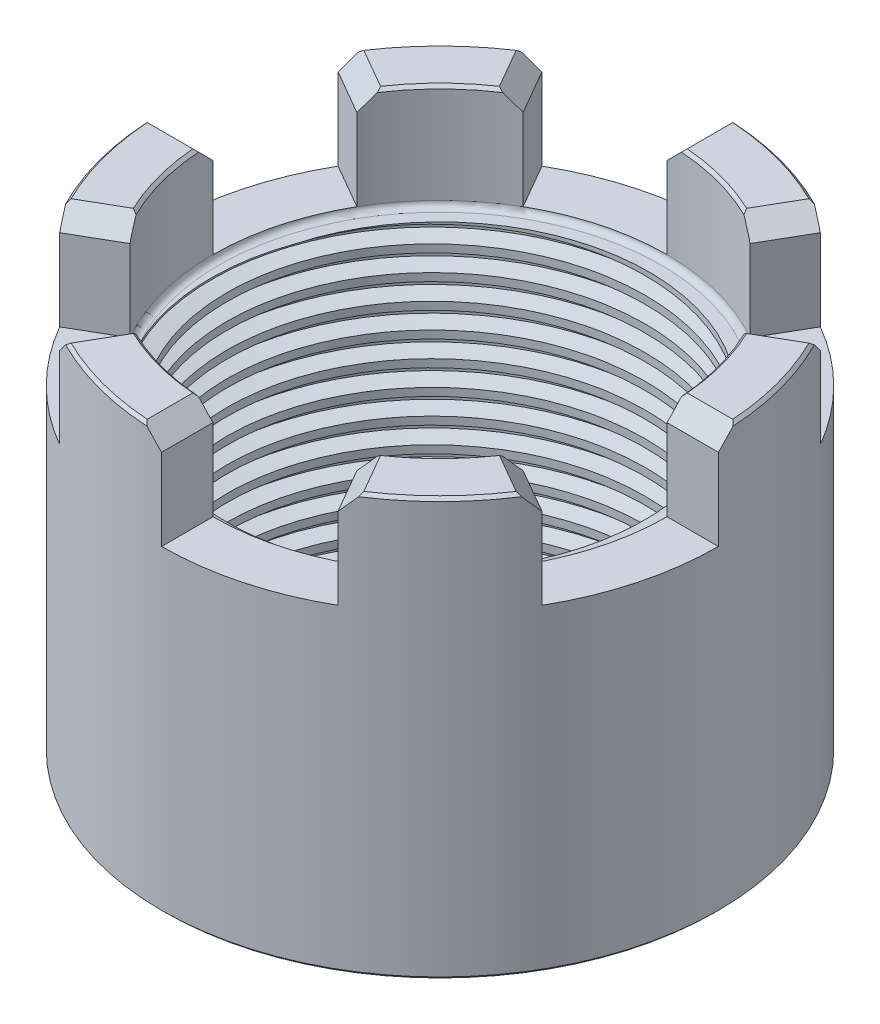
SolidWorks part; units mm, degrees
ref_plane "Front Plane" through (0, 0, 0) normal (0, 0, 1) x (1, 0, 0)
ref_plane "Top Plane" through (0, 0, 0) normal (0, 1, 0) x (1, 0, 0)
ref_plane "Right Plane" through (0, 0, 0) normal (1, 0, 0) x (0, 0, -1)
sketch "Sketch1" plane through (0, 0, 0) normal (0, 1, 0) x (1, 0, 0)
  circle A0 centre (0, 0) radius 35.56
  dimension "D1" = 71.12
extrude "Boss-Extrude1" add sketch "Sketch1" along normal blind 40.64
sketch "Sketch2" plane through (0, 40.64, 0) normal (0, 1, 0) x (1, 0, 0)
  circle A0 centre (0, 0) radius 26.7018
  dimension "D1" = 53.4035
extrude "Cut-Extrude1" cut sketch "Sketch2" against normal blind 67.31
sketch "Sketch3" plane through (0, 40.64, 0) normal (0, 1, 0) x (1, 0, 0)
  line L0 (-28.9941, 0) -> (-35.56, 0)
  line L1 (-25.1096, -14.4971) -> (-30.7959, -17.78)
  line L2 (-25.1096, 14.4971) -> (-30.7959, 17.78)
  line L3 (-14.497, 25.1096) -> (-17.78, 30.7959)
  line L4 (0, 28.9941) -> (0, 35.56)
  line L5 (14.4971, 25.1096) -> (17.78, 30.7959)
  line L6 (25.1096, 14.497) -> (30.7959, 17.78)
  line L7 (28.9941, 0) -> (35.56, 0)
  line L8 (25.1096, -14.4971) -> (30.7959, -17.78)
  line L9 (14.497, -25.1096) -> (17.78, -30.7959)
  line L10 (0, -28.9941) -> (0, -35.56)
  line L11 (-14.4971, -25.1096) -> (-17.78, -30.7959)
  arc A0 (-35.56, 0) -> (-30.7959, -17.78) centre (0, 0) ccw
  arc A1 (-28.9941, 0) -> (-25.1096, -14.4971) centre (0, 0) ccw
  arc A2 (-17.78, 30.7959) -> (-30.7959, 17.78) centre (0, 0) ccw
  arc A3 (-14.497, 25.1096) -> (-25.1096, 14.4971) centre (0, 0) ccw
  arc A4 (17.78, 30.7959) -> (0, 35.56) centre (0, 0) ccw
  arc A5 (14.4971, 25.1096) -> (0, 28.9941) centre (0, 0) ccw
  arc A6 (35.56, 0) -> (30.7959, 17.78) centre (0, 0) ccw
  arc A7 (28.9941, 0) -> (25.1096, 14.497) centre (0, 0) ccw
  arc A8 (17.78, -30.7959) -> (30.7959, -17.78) centre (0, 0) ccw
  arc A9 (14.497, -25.1096) -> (25.1096, -14.4971) centre (0, 0) ccw
  arc A10 (-17.78, -30.7959) -> (0, -35.56) centre (0, 0) ccw
  arc A11 (-14.4971, -25.1096) -> (0, -28.9941) centre (0, 0) ccw
  point P29 (0, 0)
  dimension "D2" = 57.9882
  dimension "D1" = 30
  dimension "D3" = 6
extrude "Boss-Extrude2" add sketch "Sketch3" along normal blind 12.7
chamfer "Chamfer1" distance 2.286 angle 45 1 edges at (0, 53.34, 32.2771)
chamfer "Chamfer2" distance 2.286 angle 45 1 edges at (-16.1385, 53.34, 27.9527)
chamfer "Chamfer3" distance 2.286 angle 45 1 edges at (-27.9527, 53.34, 16.1385)
chamfer "Chamfer4" distance 2.286 angle 45 1 edges at (16.1385, 53.34, 27.9527)
chamfer "Chamfer5" distance 2.286 angle 45 1 edges at (27.9527, 53.34, 16.1385)
chamfer "Chamfer6" distance 2.286 angle 45 1 edges at (32.277, 53.34, 0)
chamfer "Chamfer7" distance 2.286 angle 45 1 edges at (27.9527, 53.34, -16.1385)
chamfer "Chamfer8" distance 2.286 angle 45 1 edges at (16.1385, 53.34, -27.9527)
chamfer "Chamfer9" distance 2.286 angle 45 1 edges at (0, 53.34, -32.2771)
chamfer "Chamfer10" distance 2.286 angle 45 1 edges at (-16.1385, 53.34, -27.9527)
chamfer "Chamfer11" distance 2.286 angle 45 1 edges at (-27.9527, 53.34, -16.1385)
chamfer "Chamfer12" distance 2.286 angle 45 1 edges at (-32.2771, 53.34, 0)
chamfer "Chamfer13" distance 0.381 angle 45 1 edges at (9.2036, 53.34, -34.3483)
chamfer "Chamfer14" distance 0.381 angle 45 1 edges at (-25.1447, 53.34, -25.1447)
chamfer "Chamfer15" distance 0.381 angle 45 1 edges at (-34.3483, 53.34, 9.2036)
chamfer "Chamfer16" distance 0.381 angle 45 1 edges at (-9.2036, 53.34, 34.3483)
chamfer "Chamfer17" distance 0.381 angle 45 1 edges at (25.1447, 53.34, 25.1447)
chamfer "Chamfer18" distance 0.381 angle 45 1 edges at (34.3483, 53.34, -9.2036)
chamfer "Chamfer20" distance 0.381 angle 45 1 edges at (-28.0062, 53.34, 7.5042)
chamfer "Chamfer21" distance 0.381 angle 45 1 edges at (-7.5042, 53.34, 28.0062)
chamfer "Chamfer22" distance 0.381 angle 45 1 edges at (20.5019, 53.34, 20.5019)
chamfer "Chamfer23" distance 0.381 angle 45 1 edges at (-20.5019, 53.34, -20.5019)
chamfer "Chamfer24" distance 0.381 angle 45 1 edges at (7.5042, 53.34, -28.0062)
chamfer "Chamfer25" distance 0.381 angle 45 1 edges at (28.0062, 53.34, -7.5042)
chamfer "Chamfer26" distance 0.381 angle 45 1 edges at (0, 0, 35.56)
sketch "Sketch4" plane through (0, 40.64, 0) normal (0, 1, 0) x (1, 0, 0)
  circle A0 centre (0, 0) radius 28.9941
extrude "Cut-Extrude2" cut sketch "Sketch4" against normal blind 0.762
fillet "Fillet1" radius 0.762 1 edges at (0, 39.878, 28.9941)
chamfer "Chamfer27" distance 2.5591 angle 45 1 edges at (0, 0, 26.7018)
thread "Thread3" pitch 3.175 method cut profile "Thread Profile4" start angle 1, offset 3.302, length 0, pitch 3.175, diameter 53.4035
ref_plane "Plane4" through (-26.6977, 43.18, -0.466) normal (0.0175, 0, -0.9998) x (0.9998, 0, 0.0175)
sketch "Thread Profile4" plane through (-26.6977, 43.18, -0.466) normal (0.0175, 0, -0.9998) x (0.9998, 0, 0.0175)
  line L0 (0, 0) -> (0, 3.175) construction
  line L11 (0, 0) -> (0, 2.1748)
  line L12 (0, 2.1748) -> (-1.9291, 1.6759)
  line L13 (-1.9291, 1.6759) -> (-1.9291, 0.4989)
  line L15 (-1.9291, 0.4989) -> (0, 0)
  line L17 (-1.9291, 1.0874) -> (0, 1.0874) construction
  point P2 (0, 0)
  dimension "D1" = 29
  dimension "Pitch" = 3.175
  dimension "Profile_Land" = 1.177
  dimension "Profile_Height" = 1.9291
